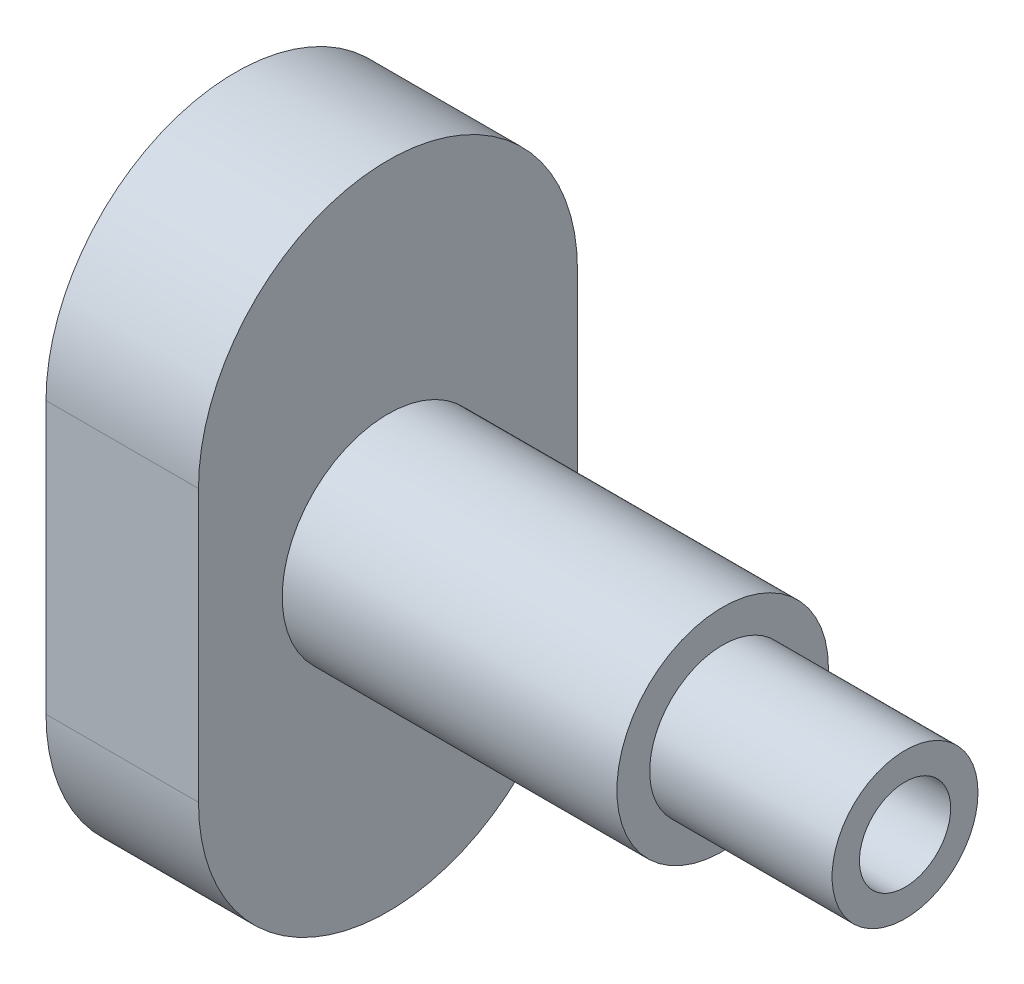
SolidWorks part; units mm, degrees
ref_plane "Front Plane" through (0, 0, 0) normal (1, 0, 0) x (0, 1, 0)
ref_plane "Top Plane" through (0, 0, 0) normal (0, 0, 1) x (0, 1, 0)
ref_plane "Right Plane" through (0, 0, 0) normal (0, 1, 0) x (-1, 0, 0)
sketch "Sketch1" plane through (0, 0, 0) normal (1, 0, 0) x (0, 1, 0)
  line L0 (-7.45, 0) -> (7.45, 0) construction
  line L1 (-7.45, 10.39) -> (7.45, 10.39)
  line L2 (-7.45, -10.39) -> (7.45, -10.39)
  arc A0 (-7.45, 10.39) -> (-7.45, -10.39) centre (-7.45, 0) ccw
  arc A1 (7.45, -10.39) -> (7.45, 10.39) centre (7.45, 0) ccw
  point P3 (0, 0)
  point P8 (0, 0)
  dimension "D2" = 14.9
  dimension "D1" = 20.78
extrude "Boss-Extrude1" add sketch "Sketch1" along normal blind 8.36
sketch "Sketch2" plane through (8.36, 0, 0) normal (1, 0, 0) x (0, 1, 0)
  circle A0 centre (0, 0) radius 5.8
  dimension "D1" = 11.6
extrude "Boss-Extrude2" add sketch "Sketch2" along normal blind 18.35
sketch "Sketch3" plane through (26.71, 0, 0) normal (1, 0, 0) x (0, 1, 0)
  circle A0 centre (0, 0) radius 4
  dimension "D1" = 8
extrude "Boss-Extrude3" add sketch "Sketch3" along normal blind 10
sketch "Sketch4" plane through (36.71, 0, 0) normal (1, 0, 0) x (0, 1, 0)
  circle A0 centre (0, 0) radius 2.5
  dimension "D1" = 5
extrude "Cut-Extrude1" cut sketch "Sketch4" against normal through all
